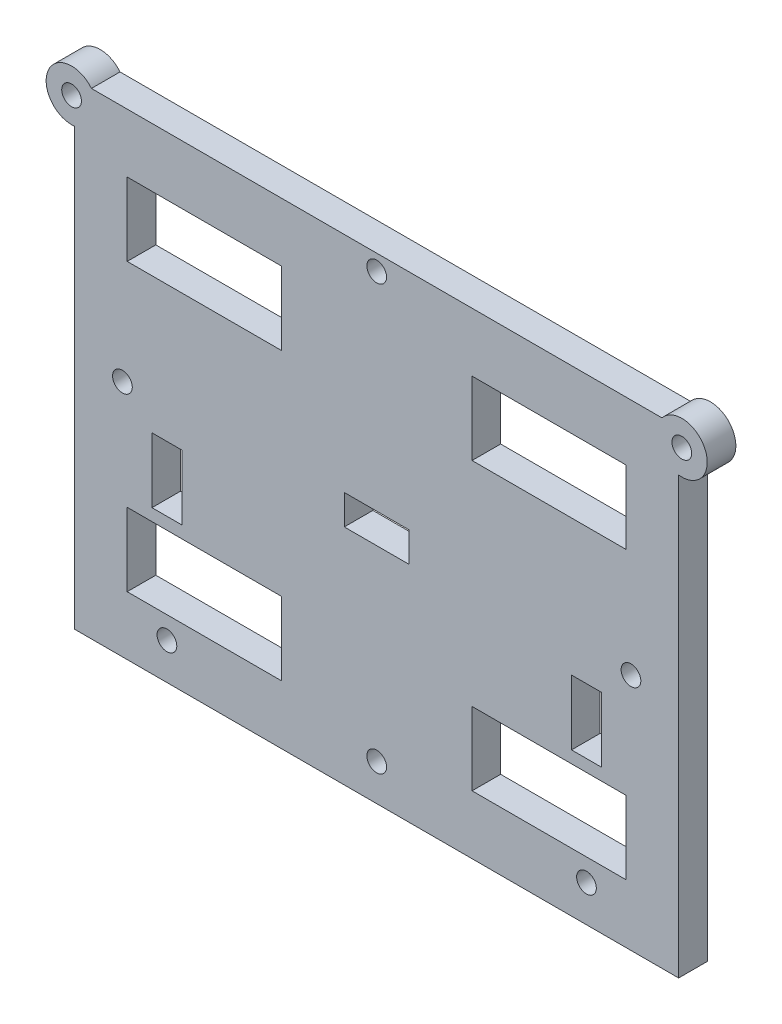
SolidWorks part; units mm, degrees
ref_plane "Front Plane" through (0, 0, 0) normal (0, 0, 1) x (1, 0, 0)
ref_plane "Top Plane" through (0, 0, 0) normal (0, 1, 0) x (1, 0, 0)
ref_plane "Right Plane" through (0, 0, 0) normal (1, 0, 0) x (0, 0, -1)
sketch "Sketch1" plane through (0, 0, 0) normal (0, 0, 1) x (1, 0, 0)
  line L0 (0, -37.5) -> (0, 37.5) construction
  line L1 (-47.5, -37.5) -> (47.5, -37.5)
  line L2 (-47.5, -37.5) -> (-47.5, 37.5)
  line L3 (-47.5, 37.5) -> (47.5, 37.5)
  line L4 (47.5, -37.5) -> (47.5, 37.5)
  line L5 (-47.5, -37.5) -> (47.5, 37.5) construction
  line L6 (-47.5, 37.5) -> (47.5, -37.5) construction
  line L7 (-47.5, 0) -> (47.5, 0) construction
  line L8 (-47.5, 22.5) -> (47.5, 22.5) construction
  line L9 (39.25, 16.75) -> (15, 28.25) construction
  line L10 (-39.25, 28.25) -> (-15, 28.25)
  line L11 (-39.25, 28.25) -> (-39.25, 16.75)
  line L12 (-39.25, 16.75) -> (-15, 16.75)
  line L13 (-15, 28.25) -> (-15, 16.75)
  line L14 (-39.25, 28.25) -> (-15, 16.75) construction
  line L15 (-39.25, 16.75) -> (-15, 28.25) construction
  line L16 (39.25, 28.25) -> (15, 16.75) construction
  line L17 (15, 28.25) -> (15, 16.75)
  line L18 (39.25, 16.75) -> (15, 16.75)
  line L19 (39.25, 28.25) -> (39.25, 16.75)
  line L20 (39.25, 28.25) -> (15, 28.25)
  line L21 (39.25, -28.25) -> (15, -16.75) construction
  line L22 (-39.25, -16.75) -> (-15, -28.25) construction
  line L23 (-39.25, -28.25) -> (-15, -16.75) construction
  line L24 (39.25, -16.75) -> (15, -28.25) construction
  line L25 (39.25, -28.25) -> (15, -28.25)
  line L26 (39.25, -28.25) -> (39.25, -16.75)
  line L27 (39.25, -16.75) -> (15, -16.75)
  line L28 (15, -28.25) -> (15, -16.75)
  line L29 (-15, -28.25) -> (-15, -16.75)
  line L30 (-39.25, -16.75) -> (-15, -16.75)
  line L31 (-39.25, -28.25) -> (-39.25, -16.75)
  line L32 (-39.25, -28.25) -> (-15, -28.25)
  point P0 (0, 0)
  point P12 (-27.125, 22.5)
  point P21 (27.125, 22.5)
  point P30 (27.125, -22.5)
  point P31 (-27.125, -22.5)
  dimension "D1" = 95
  dimension "D2" = 75
  dimension "D3" = 22.5
  dimension "D4" = 24.25
  dimension "D5" = 11.5
  dimension "D6" = 15
extrude "Boss-Extrude1" add sketch "Sketch1" along normal blind 4.5
sketch "Sketch8" plane through (0, 0, 4.5) normal (0, 0, 1) x (1, 0, 0)
  line L0 (-47.5, 37.5) -> (-47.5, -37.5) construction
  line L1 (47.5, -37.5) -> (47.5, 37.5) construction
  circle A0 centre (-47.5, 29.5) radius 8
  circle A1 centre (47.5, 29.5) radius 8
  dimension "D1" = 16
extrude "Boss-Extrude2" [suppressed] add sketch "Sketch8" against normal through all
sketch "Sketch2" plane through (0, 0, 4.5) normal (0, 0, 1) x (1, 0, 0)
  line L0 (0, -37.5) -> (0, 37.5) construction
  line L1 (-47.5, -37.5) -> (47.5, -37.5) construction
  line L2 (47.5, 37.5) -> (-47.5, 37.5) construction
  line L3 (-47.5, 0) -> (47.5, 0) construction
  line L4 (-47.5, 37.5) -> (-47.5, -37.5) construction
  line L5 (47.5, -37.5) -> (47.5, 37.5) construction
  line L6 (-40, 0) -> (40, 0) construction
  line L7 (-48, 35) -> (48, 35) construction
  circle A0 centre (-48, 35) radius 1.55
  circle A1 centre (48, 35) radius 1.55
  circle A2 centre (40, 0) radius 1.55
  circle A3 centre (-40, 0) radius 1.55
  circle A4 centre (0, 35) radius 1.55
  dimension "D1" = 3.1
  dimension "D7" = 3.1
  dimension "D8" = 3.1
  dimension "D9" = 3.1
  dimension "D2" = 48
  dimension "D3" = 35
  dimension "D4" = 80
  dimension "D5" = 40
  dimension "D6" = 0
extrude "screwHoles" cut sketch "Sketch2" against normal through all
sketch "Sketch3" plane through (0, 0, 4.5) normal (0, 0, 1) x (1, 0, 0)
  line L0 (-47.5, 16.9836) -> (26.0486, 16.9836) construction
  line L1 (-47.5, 37.5) -> (-47.5, 36.4671) construction
  line L3 (0, 37.5) -> (0, -37.5) construction
  line L4 (47.5, 37.5) -> (-47.5, 37.5) construction
  line L5 (-47.5, -37.5) -> (47.5, -37.5) construction
  line L6 (19.1, 14.6336) -> (8.9, 19.3336) construction
  line L7 (-19.1, 19.3336) -> (-8.9, 19.3336)
  line L8 (-19.1, 19.3336) -> (-19.1, 14.6336)
  line L9 (-19.1, 14.6336) -> (-8.9, 14.6336)
  line L10 (-8.9, 19.3336) -> (-8.9, 14.6336)
  line L11 (-19.1, 19.3336) -> (-8.9, 14.6336) construction
  line L12 (-19.1, 14.6336) -> (-8.9, 19.3336) construction
  line L13 (19.1, 19.3336) -> (8.9, 14.6336) construction
  line L14 (8.9, 19.3336) -> (8.9, 14.6336)
  line L15 (19.1, 14.6336) -> (8.9, 14.6336)
  line L16 (19.1, 19.3336) -> (19.1, 14.6336)
  line L17 (19.1, 19.3336) -> (8.9, 19.3336)
  line L18 (-47.5, 37.5) -> (-47.5, 36.4671) construction
  point P2 (-47.5, 36.9836)
  point P12 (-14, 16.9836)
  point P21 (14, 16.9836)
  dimension "D1" = 10.2
  dimension "D2" = 4.7
  dimension "D3" = 14
  dimension "D4" = 20
extrude "BeltClamp" [suppressed] cut sketch "Sketch3" against normal through all
sketch "Sketch4" plane through (0, 0, 4.5) normal (0, 0, 1) x (1, 0, 0)
  line L0 (-47.5, 0) -> (47.5, 0) construction
  line L1 (-47.5, 37.5) -> (-47.5, 36.4671) construction
  line L2 (47.5, -37.5) -> (47.5, 33.5329) construction
  line L4 (-5.1, 2.35) -> (5.1, 2.35)
  line L5 (-5.1, 2.35) -> (-5.1, -2.35)
  line L6 (-5.1, -2.35) -> (5.1, -2.35)
  line L7 (5.1, 2.35) -> (5.1, -2.35)
  line L8 (-5.1, 2.35) -> (5.1, -2.35) construction
  line L9 (-5.1, -2.35) -> (5.1, 2.35) construction
  circle A0 centre (-40, 0) radius 1.55 construction
  point P6 (0, 0)
  dimension "D1" = 10.2
  dimension "D2" = 4.7
  dimension "D3" = 0
extrude "Cut-Extrude3" cut sketch "Sketch4" against normal through all
sketch "Sketch5" plane through (0, 0, 4.5) normal (0, 0, 1) x (1, 0, 0)
  line L0 (-47.5, -9.75) -> (47.5, -9.75) construction
  line L1 (-47.5, 37.5) -> (-47.5, 36.4671) construction
  line L2 (47.5, -37.5) -> (47.5, 33.5329) construction
  line L3 (5.1, -2.35) -> (5.1, 2.35) construction
  line L4 (0, -37.5) -> (0, 37.5) construction
  line L5 (-47.5, -37.5) -> (47.5, -37.5) construction
  line L6 (47.5, 37.5) -> (-47.5, 37.5) construction
  line L7 (-30.65, -14.85) -> (-35.35, -4.65) construction
  line L8 (30.65, -4.65) -> (35.35, -4.65)
  line L9 (30.65, -4.65) -> (30.65, -14.85)
  line L10 (30.65, -14.85) -> (35.35, -14.85)
  line L11 (35.35, -4.65) -> (35.35, -14.85)
  line L12 (30.65, -4.65) -> (35.35, -14.85) construction
  line L13 (30.65, -14.85) -> (35.35, -4.65) construction
  line L14 (-30.65, -4.65) -> (-35.35, -14.85) construction
  line L15 (-35.35, -4.65) -> (-35.35, -14.85)
  line L16 (-30.65, -14.85) -> (-35.35, -14.85)
  line L17 (-30.65, -4.65) -> (-30.65, -14.85)
  line L18 (-30.65, -4.65) -> (-35.35, -4.65)
  line L19 (33, -9.75) -> (33, -37.5) construction
  line L20 (-33, -9.75) -> (-33, -37.5) construction
  line L21 (-33, -31.75) -> (33, -31.75) construction
  circle A0 centre (33, -31.75) radius 1.55
  circle A1 centre (-33, -31.75) radius 1.55
  circle A2 centre (0, -31.75) radius 1.55
  point P6 (5.1, 0)
  point P15 (33, -9.75)
  point P24 (-33, -9.75)
  dimension "D7" = 3.1
  dimension "D5" = 3.1
  dimension "D1" = 9.75
  dimension "D2" = 10.2
  dimension "D3" = 4.7
  dimension "D4" = 33
  dimension "D6" = 22
extrude "Cut-Extrude4" cut sketch "Sketch5" against normal through all
sketch "Sketch9" plane through (0, 0, 4.5) normal (0, 0, 1) x (1, 0, 0)
  line L0 (47.5, 37.5) -> (-47.5, 37.5) construction
  line L1 (0, 37.5) -> (0, -37.5) construction
  line L2 (-47.5, -37.5) -> (47.5, -37.5) construction
  line L3 (50.5, 35) -> (45.5, 35) construction
  line L4 (-50.5, 35) -> (-45.5, 35) construction
  circle A0 centre (-48, 35) radius 4
  circle A1 centre (-48, 35) radius 1.55
  arc A2 (-47.5, 33.5329) -> (-47.5, 36.4671) centre (-48, 35) ccw construction
  circle A3 centre (48, 35) radius 1.55
  circle A4 centre (48, 35) radius 4
  point P17 (0, -37.5)
  dimension "D1" = 8
extrude "Boss-Extrude3" add sketch "Sketch9" against normal through all
equation "\"X-ROD-SPACING\"=45"
equation "\"Y-ROD-SPACING\"=75"
equation "\"Z-ROD-SPACING\"=17.5"
equation "\"Y-BED-OFFSET\"=2"
equation "\"Y-BED-ROD-INSET\"=3.5"
equation "\"Y-BED-SCREW-SPACING\"=209"
equation "\"Y-BED-SCREW-CUTOUT-SLOT-HEIGHT\"=2"
equation "\"T-SLOT-NUT-FILLET-RADIUS\"=0.25"
equation "\"T-SLOT-SCREW-SHAFT-RADIUS\"=1.75"
equation "\"T-SLOT-SCREW-SHAFT-CUTOUT-LENGTH\"=10.5"
equation "\"T-SLOT-NUT-DEPTH\"=4.2"
equation "\"T-SLOT-NUT-WIDTH\"=3"
equation "\"T-SLOT-NUT-END-DISTANCE\"=8"
equation "\"ACRYLIC-THICKNESS\"=10"
equation "\"ACRYLIC-THICKNESS2\"=4.5"
equation "\"ACRYLIC-TAB-CUTOUT-SIZE\"=\"ACRYLIC-THICKNESS\"+\"ACRYLIC-TAB-TOLERANCE\"*2"
equation "\"ACRYLIC-TAB-WIDTH\"=\"ACRYLIC-THICKNESS\""
equation "\"ACRYLIC-M3-HOLE\"=3.1"
equation "\"SMOOTHROD-CAP-SCREW-DISTANCE\"=20"
equation "\"FRAME-WIDTH-INNER\"=370"
equation "\"NEMA17-HOLE-SPACING\"=31"
equation "\"NEMA17-CENTRAL-CUTOUT\"=22.5"
equation "\"Z-BRACKET-REACH\"=55"
equation "\"Z-ROD-INSET\"=16"
equation "\"TOP-BRACKET-SPACING\"=40"
equation "\"SMOOTHROD-X-LENGTH\"=350"
equation "\"SMOOTHROD-Y-LENGTH\"=350"
equation "\"SMOOTHROD-Z-LENGTH\"=350"
equation "\"SMOOTHROD-TIGHTENING-HEADROOM\"=.25"
equation "\"LEADSCREW-Z-LENGTH\"=300"
equation "\"SCREW-LENGTH-FRAME\"=\"ACRYLIC-THICKNESS\" + 10"
equation "\"SCREW-LENGTH-MOTOR\"=\"ACRYLIC-THICKNESS\" + 5"
equation "\"SCREW-HEAD-RADIUS\"=6"
equation "\"PRINTED-X-SMOOTHROD-DIAMETER\"=8.2"
equation "\"PRINTED-X-SMOOTHROD-CUTOUT\"=10"
equation "\"PRINTED-X-BASE-HEIGHT\"=10"
equation "\"PRINTED-LM8UU-CUTOUT-SIZE\"=15.25"
equation "\"PRINTED-LM8UU-CUTOUT-LENGTH\"=24.5"
equation "\"PRINTED-X-IDLER-HEIGHT\"=16"
equation "\"PSU-MOUNTING-WIDTH\"=95"
equation "\"PSU-MOUNTING-HEIGHT\"=177"
equation "\"Y-BELT-TO-ROD-DISTANCE\"=20"
equation "\"SPOOL-HOLDER-ROD-SPACING\"=150"
equation "\"D3@Sketch1\"=\"X-ROD-SPACING\"/2"
equation "\"D4@Sketch1\"=\"ACRYLIC-X-CARRIAGE-LM8UU-CUTOUT-WIDTH\""
equation "\"D1@Boss-Extrude1\"=\"ACRYLIC-THICKNESS2\""
equation "\"D1@Sketch2\"=\"ACRYLIC-M3-HOLE\""
equation "\"D1@Sketch3\"=\"ACRYLIC-TAB-CUTOUT-SIZE\""
equation "\"D2@Sketch3\"=\"ACRYLIC-THICKNESS2\"+\"ACRYLIC-TAB-TOLERANCE\"*2"
equation "\"ACRYLIC-X-CARRIAGE-WIDTH\"=55"
equation "\"ACRYLIC-X-CARRIAGE-HEIGHT\"=75"
equation "\"D2@Sketch1\"=\"ACRYLIC-X-CARRIAGE-HEIGHT\""
equation "\"ACRYLIC-X-CARRIAGE-CENTER-TAB-SPACING\"=14"
equation "\"D3@Sketch3\"=\"ACRYLIC-X-CARRIAGE-CENTER-TAB-SPACING\""
equation "\"SCREW-LENGTH-EXTRUDER\"=28"
equation "\"ACRYLIC-X-CARRIAGE-SCREW-SPACING-X\"=15"
equation "\"ACRYLIC-X-CARRIAGE-SCREW-SPACING-Y\"=33"
equation "\"D1@Sketch4\"=\"ACRYLIC-TAB-CUTOUT-SIZE\""
equation "\"D2@Sketch4\"=\"ACRYLIC-THICKNESS2\"+\"ACRYLIC-TAB-TOLERANCE\"*2"
equation "\"D2@Sketch5\"=\"ACRYLIC-TAB-CUTOUT-SIZE\""
equation "\"D3@Sketch5\"=\"ACRYLIC-THICKNESS2\"+\"ACRYLIC-TAB-TOLERANCE\"*2"
equation "\"ACRYLIC-X-CARRIAGE-EXTRUDER-SHELF-DEPTH\"=\"ACRYLIC-X-CARRIAGE-EXTRUDER-OFFSET\" + 28"
equation "\"ACRYLIC-X-CARRIAGE-EXTRUDER-BRACE-SPACING\"=23"
equation "\"D4@Sketch5\"=\"ACRYLIC-X-CARRIAGE-DUAL-MOUNT-BRACE-WIDTH\""
equation "\"D1@Sketch5\"=\"ACRYLIC-THICKNESS2\"/2 + 7.5"
equation "\"D4@Sketch2\"=\"ACRYLIC-X-CARRIAGE-DUAL-MOUNT-SCREW-WIDTH\"*2"
equation "\"D5@Sketch2\"=\"ACRYLIC-X-CARRIAGE-DUAL-MOUNT-SCREW-WIDTH\""
equation "\"D7@Sketch2\"=\"ACRYLIC-M3-HOLE\""
equation "\"D8@Sketch2\"=\"ACRYLIC-M3-HOLE\""
equation "\"ACRYLIC-X-CARRIAGE-LM8UU-CUTOUT-WIDTH\"=24.25"
equation "\"ACRYLIC-TAB-TOLERANCE\"=.1"
equation "\"ACRYLIC-X-CARRIAGE-EXTRUDER-OFFSET\"=26"
equation "\"ACRYLIC-X-CARRIAGE-EXTRUDER-ANGLE\"=90"
equation "\"ACRYLIC-X-CARRIAGE-EXTRUDER-BRACE-TAB-OFFSET\"=20"
equation "\"ACRYLIC-X-CARRIAGE-EXTRUDER-BRACE-HEIGHT\"=35"
equation "\"ACRYLIC-X-CARRIAGE-EXTRUDER-BRACE-SCREW-SPACING\"=22"
equation "\"D5@Sketch5\"=\"ACRYLIC-M3-HOLE\""
equation "\"ACRYLIC-X-CARRIAGE-DUAL-WIDTH-MULTIPLIER\"=1.65"
equation "\"ACRYLIC-X-CARRIAGE-DUAL-HOTEND-SPACING\"=42"
equation "\"ACRYLIC-X-CARRIAGE-DUAL-WIDTH\"=95"
equation "\"ACRYLIC-X-CARRIAGE-DUAL-HOTEND-SEPARATION\"=35"
equation "\"ACRYLIC-X-CARRIAGE-DUAL-MOUNT-PLATE-DEPTH\"=75"
equation "\"ACRYLIC-X-CARRIAGE-DUAL-MOUNT-BRACE-WIDTH\"=33"
equation "\"ACRYLIC-X-CARRIAGE-DUAL-MOUNT-SCREW-WIDTH\"=40"
equation "\"D1@Sketch1\"=\"ACRYLIC-X-CARRIAGE-DUAL-WIDTH\""
equation "\"D9@Sketch2\"=\"ACRYLIC-M3-HOLE\""
equation "\"D7@Sketch5\"=\"ACRYLIC-M3-HOLE\""
equation "\"ACRYLIC-X-CARRIAGE-LM8UU-CUTOUT-HEIGHT\"=11.5"
equation "\"D5@Sketch1\"=\"ACRYLIC-X-CARRIAGE-LM8UU-CUTOUT-HEIGHT\""
